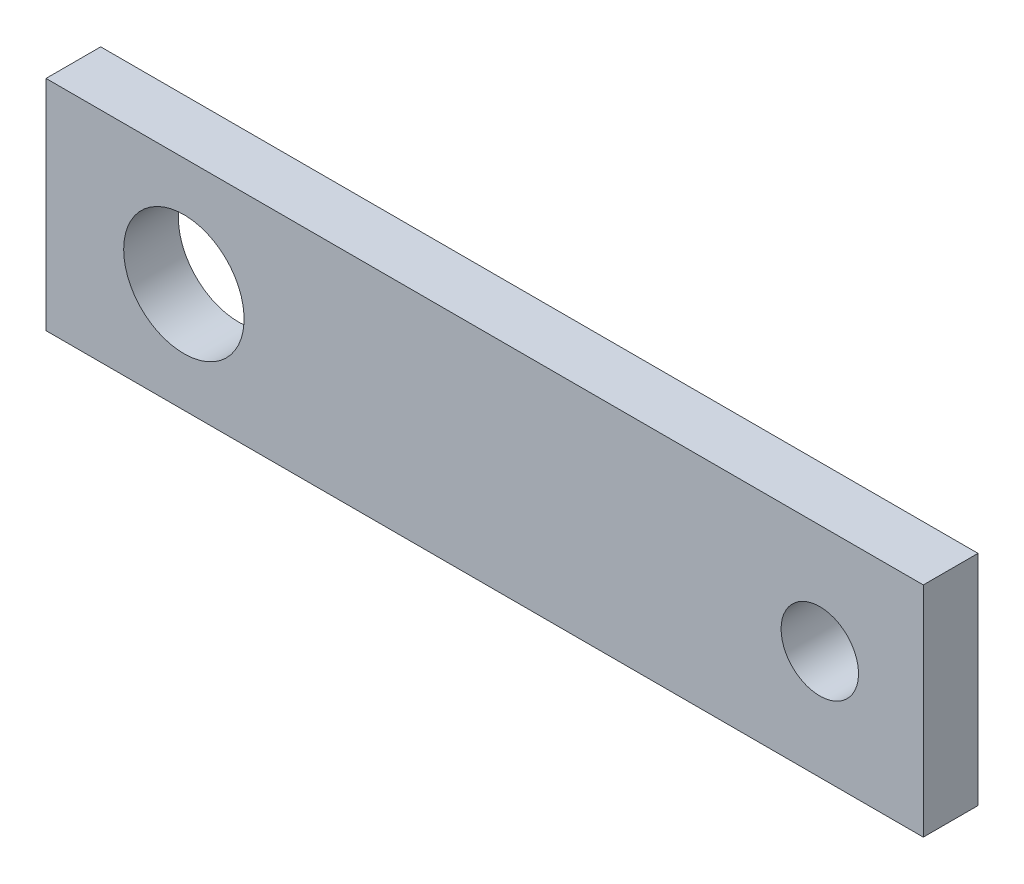
SolidWorks part; units mm, degrees
material "Cobre"
ref_plane "Plano frontal" through (0, 0, 0) normal (0, 0, 1) x (1, 0, 0)
ref_plane "Plano superior" through (0, 0, 0) normal (0, 1, 0) x (1, 0, 0)
ref_plane "Plano direito" through (0, 0, 0) normal (1, 0, 0) x (0, 0, -1)
sketch "Esboço1" plane through (0, 0, 0) normal (0, 0, 1) x (1, 0, 0)
  line L1 (25.5, 6.35) -> (-25.5, 6.35)
  line L2 (25.5, 6.35) -> (25.5, -6.35)
  line L3 (25.5, -6.35) -> (-25.5, -6.35)
  line L4 (-25.5, 6.35) -> (-25.5, -6.35)
  line L5 (25.5, 6.35) -> (-25.5, -6.35) construction
  line L6 (25.5, -6.35) -> (-25.5, 6.35) construction
  point P0 (0, 0)
  dimension "D1" = 51
  dimension "D2" = 12.7
base flange "Flange-base1" sketch "Esboço1" thickness 3.18 reverse thickness direction no parameters "D1"=0.7366
sketch "Esboço2" plane through (0, 0, -3.18) normal (0, 0, -1) x (-1, 0, 0)
  line L0 (-25.5, 6.35) -> (-13.465, -6.35) construction
  line L1 (25.5, -6.35) -> (-25.5, -6.35) construction
  line L2 (-13.465, 42.4923) -> (-13.465, -42.5077) construction
  circle A0 centre (17.485, 0) radius 3.5
  circle A1 centre (-19.4825, 0) radius 2.25
  dimension "D1" = 7
  dimension "D2" = 4.5
extrude "Corte-extrusão1" cut sketch "Esboço2" against normal blind 10 normal cut yes
sketch "Curva-Linhas1" [suppressed] plane through (0, 0, 0) normal (0, 1, 0) x (1, 0, 0)
sketch "Caixa delimitadora1" [suppressed] plane through (0, 0, 0) normal (0, 1, 0) x (1, 0, 0)
sheet metal parameters "Chapa metálica1" thickness 3.18 parameters "D1"=0.7366
flat pattern "Padrão-Plano1" [suppressed]
sketch "Curva-Linhas2" plane through (0, 0, 0) normal (0, 0, 1) x (1, 0, 0)
sketch3d "Caixa delimitadora2" [suppressed]
  line L0 (-25.5, -6.35, 0) -> (25.5, -6.35, 0) construction
  line L1 (-25.5, 6.35, 0) -> (25.5, 6.35, 0) construction
  line L2 (-25.5, -6.35, 0) -> (-25.5, 6.35, 0) construction
  line L3 (25.5, -6.35, 0) -> (25.5, 6.35, 0) construction
sheet metal parameters "Chapa metálica2" thickness 3.18 parameters "D1"=0.7366
flat pattern "Padrão-Plano1"
sketch "Curva-Linhas2" plane through (0, 0, 0) normal (0, 0, 1) x (1, 0, 0)
sketch3d "Caixa delimitadora2" [suppressed]
  line L0 (-25.5, -6.35, 0) -> (25.5, -6.35, 0) construction
  line L1 (-25.5, 6.35, 0) -> (25.5, 6.35, 0) construction
  line L2 (-25.5, -6.35, 0) -> (-25.5, 6.35, 0) construction
  line L3 (25.5, -6.35, 0) -> (25.5, 6.35, 0) construction
